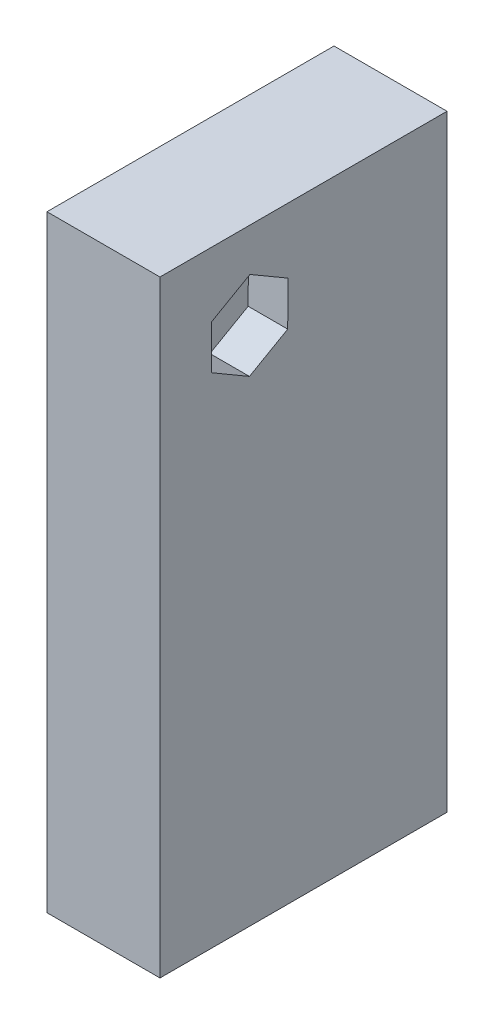
SolidWorks part; units mm, degrees
ref_plane "Front" through (0, 0, 0) normal (0, 0, 1) x (1, 0, 0)
ref_plane "Top" through (0, 0, 0) normal (0, 1, 0) x (1, 0, 0)
ref_plane "Right" through (0, 0, 0) normal (1, 0, 0) x (0, 0, -1)
sketch "Sketch1" plane through (0, 0, 0) normal (0, 0, 1) x (1, 0, 0)
  line L0 (104.7484, -27.117) -> (104.7484, -134.5537)
  line L1 (104.7484, -134.5537) -> (84.7484, -134.5537)
  line L2 (84.7484, -134.5537) -> (84.7484, -27.117)
  line L3 (84.7484, -27.117) -> (104.7484, -27.117)
  line L4 (89.6039, -26.617) -> (80.1571, -26.617) construction
  line L5 (-159.7042, -134.5537) -> (-172.4042, -134.5537) construction
  point P6 (84.8805, -26.617)
  dimension "D1" = 0.5
  dimension "D2" = 0
  dimension "D3" = 20
extrude "Boss-Extrude1" add sketch "Sketch1" against normal blind 50.8
sketch "Sketch3" plane through (84.7484, 0, 0) normal (-1, 0, 0) x (0, 0, 1)
  line L1 (-9.1448, -38.5475) -> (-15.9144, -34.6846)
  line L2 (-15.9144, -34.6846) -> (-22.6446, -38.6157)
  line L3 (-22.6446, -38.6157) -> (-22.6052, -46.4099)
  line L4 (-22.6052, -46.4099) -> (-15.8356, -50.2728)
  line L5 (-15.8356, -50.2728) -> (-9.1054, -46.3416)
  line L6 (-9.1054, -46.3416) -> (-9.1448, -38.5475)
  circle A0 centre (-15.875, -42.4787) radius 6.75 construction
extrude "Cut-Extrude2" cut sketch "Sketch3" against normal blind 7
sketch "Sketch4" plane through (104.7484, 0, 0) normal (1, 0, 0) x (0, 0, -1)
  line L0 (15.8356, -50.2728) -> (9.1054, -46.3416) construction
  line L1 (9.1054, -46.3416) -> (9.1448, -38.5475) construction
  line L2 (9.1448, -38.5475) -> (15.9144, -34.6846) construction
  line L3 (15.9144, -34.6846) -> (22.6446, -38.6157) construction
  line L4 (22.6446, -38.6157) -> (22.6052, -46.4099) construction
  line L5 (22.6052, -46.4099) -> (15.8356, -50.2728) construction
  line L6 (15.8356, -50.2728) -> (9.1054, -46.3416)
  line L7 (9.1054, -46.3416) -> (9.1448, -38.5475)
  line L8 (9.1448, -38.5475) -> (15.9144, -34.6846)
  line L9 (15.9144, -34.6846) -> (22.6446, -38.6157)
  line L10 (22.6446, -38.6157) -> (22.6052, -46.4099)
  line L11 (22.6052, -46.4099) -> (15.8356, -50.2728)
extrude "Cut-Extrude3" cut sketch "Sketch4" against normal blind 7
